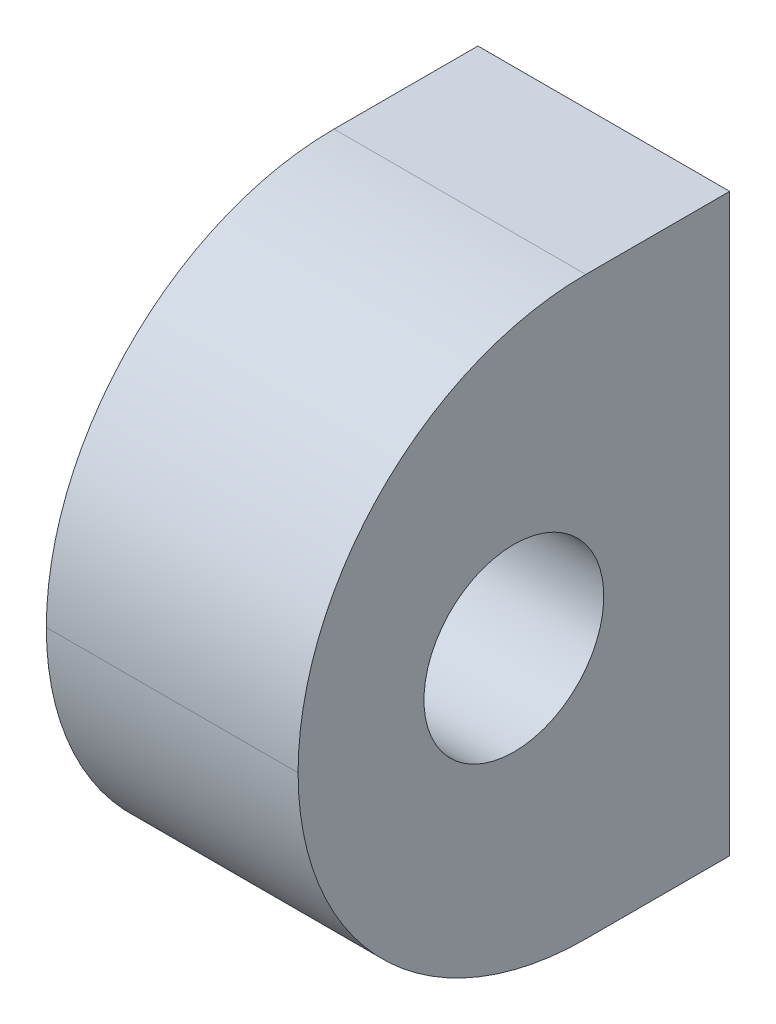
SolidWorks part; units mm, degrees
material "6061-T6 (SS)"
ref_plane "Front Plane" through (0, 0, 0) normal (0, 0, 1) x (1, 0, 0)
ref_plane "Top Plane" through (0, 0, 0) normal (0, 1, 0) x (1, 0, 0)
ref_plane "Right Plane" through (0, 0, 0) normal (1, 0, 0) x (0, 0, -1)
sketch "Sketch1" plane through (0, 0, 0) normal (0, 0, 1) x (1, 0, 0)
  line L1 (0, 0) -> (22.225, 0)
  line L2 (0, 0) -> (0, 50.8)
  line L3 (0, 50.8) -> (22.225, 50.8)
  line L4 (22.225, 0) -> (22.225, 50.8)
  dimension "D1" = 22.225
  dimension "D2" = 50.8
extrude "Boss-Extrude1" add sketch "Sketch1" along normal blind 38.1
fillet "Fillet1" radius 25.4 2 edges at (11.1125, 0, 38.1) (11.1125, 50.8, 38.1)
sketch "Sketch2" plane through (22.225, 0, 0) normal (1, 0, 0) x (0, 0, -1)
  circle A0 centre (-19.05, 25.4) radius 7.9375
  dimension "D2" = 15.875
  dimension "D1" = 19.05
extrude "Cut-Extrude1" cut sketch "Sketch2" against normal blind 38.1
